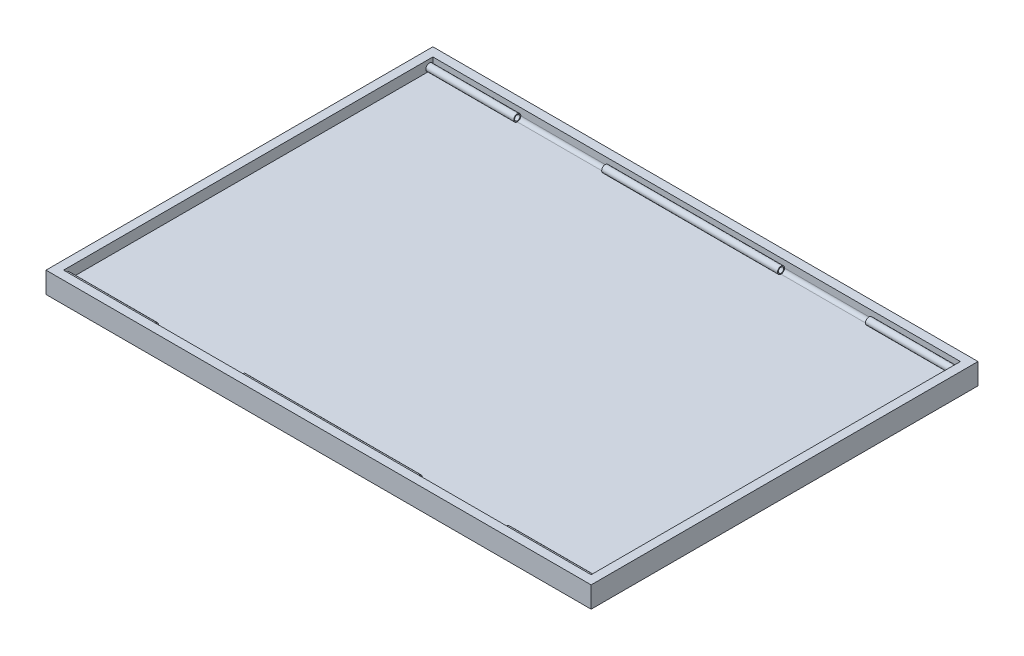
SolidWorks part; units mm, degrees
ref_plane "前视基准面" through (0, 0, 0) normal (0, 0, 1) x (1, 0, 0)
ref_plane "上视基准面" through (0, 0, 0) normal (0, 1, 0) x (1, 0, 0)
ref_plane "右视基准面" through (0, 0, 0) normal (1, 0, 0) x (0, 0, -1)
sketch "草图1" plane through (0, 0, 0) normal (0, 1, 0) x (1, 0, 0)
  line L1 (-154.3396, 132.8302) -> (155.6604, 132.8302)
  line L2 (-154.3396, 132.8302) -> (-154.3396, -87.1698)
  line L3 (-154.3396, -87.1698) -> (155.6604, -87.1698)
  line L4 (155.6604, 132.8302) -> (155.6604, -87.1698)
  dimension "D1" = 310
  dimension "D2" = 220
extrude "凸台-拉伸1" add sketch "草图1" along normal blind 12
sketch "草图2" plane through (0, 12, 0) normal (0, 1, 0) x (1, 0, 0)
  line L0 (-154.3396, 132.8302) -> (-154.3396, -87.1698) construction
  line L1 (-149.3396, 127.8302) -> (150.6604, 127.8302)
  line L2 (-149.3396, 127.8302) -> (-149.3396, -82.1698)
  line L3 (-149.3396, -82.1698) -> (150.6604, -82.1698)
  line L4 (150.6604, 127.8302) -> (150.6604, -82.1698)
  line L5 (155.6604, -87.1698) -> (155.6604, 132.8302) construction
  line L6 (155.6604, 132.8302) -> (-154.3396, 132.8302) construction
  line L7 (-154.3396, -87.1698) -> (155.6604, -87.1698) construction
  dimension "D1" = 5
  dimension "D2" = 5
  dimension "D3" = 5
  dimension "D4" = 5
extrude "切除-拉伸4" cut sketch "草图2" against normal blind 6
ref_plane "基准面2" through (150.6604, 0, 0) normal (1, 0, 0) x (0, 0, -1)
sketch "草图6" plane through (0, 6, 0) normal (0, 1, 0) x (1, 0, 0)
  line L0 (150.6604, -6.6) -> (150.6604, 6.6) construction
  line L1 (-149.3396, 127.8302) -> (150.6604, 127.8302)
  line L2 (-149.3396, 127.8302) -> (-149.3396, 125.8302)
  line L3 (-149.3396, 125.8302) -> (150.6604, 125.8302)
  line L4 (150.6604, 127.8302) -> (150.6604, 125.8302)
  line L6 (-149.3396, -82.1698) -> (150.6604, -82.1698)
  line L7 (-149.3396, -82.1698) -> (-149.3396, -80.1698)
  line L8 (-149.3396, -80.1698) -> (150.6604, -80.1698)
  line L9 (150.6604, -82.1698) -> (150.6604, -80.1698)
  dimension "D1" = 2
  dimension "D2" = 2
extrude "凸台-拉伸3" add sketch "草图6" along normal blind 2
sketch "草图8" plane through (150.6604, 0, 0) normal (1, 0, 0) x (0, 0, -1)
  line L0 (-87.1698, 12) -> (-87.1698, 0) construction
  line L1 (-87.1698, 12) -> (132.8302, 12) construction
  circle A0 centre (-80.1698, 8) radius 2
  dimension "D1" = 7
  dimension "D2" = 4
extrude "切除-拉伸5" cut sketch "草图8" against normal blind 300
extrude "拉伸-薄壁1" add sketch "草图8<2>" against normal blind 300 thin thin type one direction reverse wall 0.5
sketch "草图8<2>" plane through (150.6604, 0, 0) normal (1, 0, 0) x (0, 0, -1) same geometry as "草图8"
sketch "草图10" plane through (150.6604, 0, 0) normal (1, 0, 0) x (0, 0, -1)
  line L0 (132.8302, 12) -> (132.8302, 0) construction
  line L1 (-87.1698, 12) -> (132.8302, 12) construction
  circle A0 centre (125.8302, 8) radius 2
  dimension "D1" = 7
  dimension "D2" = 4
extrude "切除-拉伸6" cut sketch "草图10" against normal blind 300
extrude "拉伸-薄壁2" add sketch "草图10<2>" against normal blind 300 thin thin type one direction reverse wall 0.5
sketch "草图10<2>" plane through (150.6604, 0, 0) normal (1, 0, 0) x (0, 0, -1) same geometry as "草图10"
ref_plane "基准面3" through (100.6604, 0, 0) normal (1, 0, 0) x (0, 0, -1)
ref_plane "基准面4" through (-49.3396, 0, 0) normal (1, 0, 0) x (0, 0, -1)
sketch "草图12" plane through (100.6604, 0, 0) normal (1, 0, 0) x (0, 0, -1)
  line L0 (-87.1698, 12) -> (-87.1698, 0) construction
  line L1 (-87.1698, 12) -> (132.8302, 12) construction
  line L2 (132.8302, 12) -> (132.8302, 0) construction
  circle A0 centre (-80.1698, 8) radius 2
  circle A1 centre (125.8302, 8) radius 2
  dimension "D1" = 4
  dimension "D4" = 7
  dimension "D2" = 7
  dimension "D3" = 4
  dimension "D5" = 4
extrude "切除-拉伸7" cut sketch "草图12" against normal blind 50
sketch "草图13" plane through (-49.3396, 0, 0) normal (1, 0, 0) x (0, 0, -1)
  line L0 (-87.1698, 12) -> (-87.1698, 0) construction
  line L1 (-87.1698, 12) -> (132.8302, 12) construction
  line L2 (132.8302, 12) -> (132.8302, 0) construction
  circle A0 centre (-80.1698, 8) radius 2
  circle A1 centre (125.8302, 8) radius 2
  dimension "D1" = 7
  dimension "D3" = 7
  dimension "D2" = 4
  dimension "D4" = 4
extrude "切除-拉伸8" cut sketch "草图13" against normal blind 50
